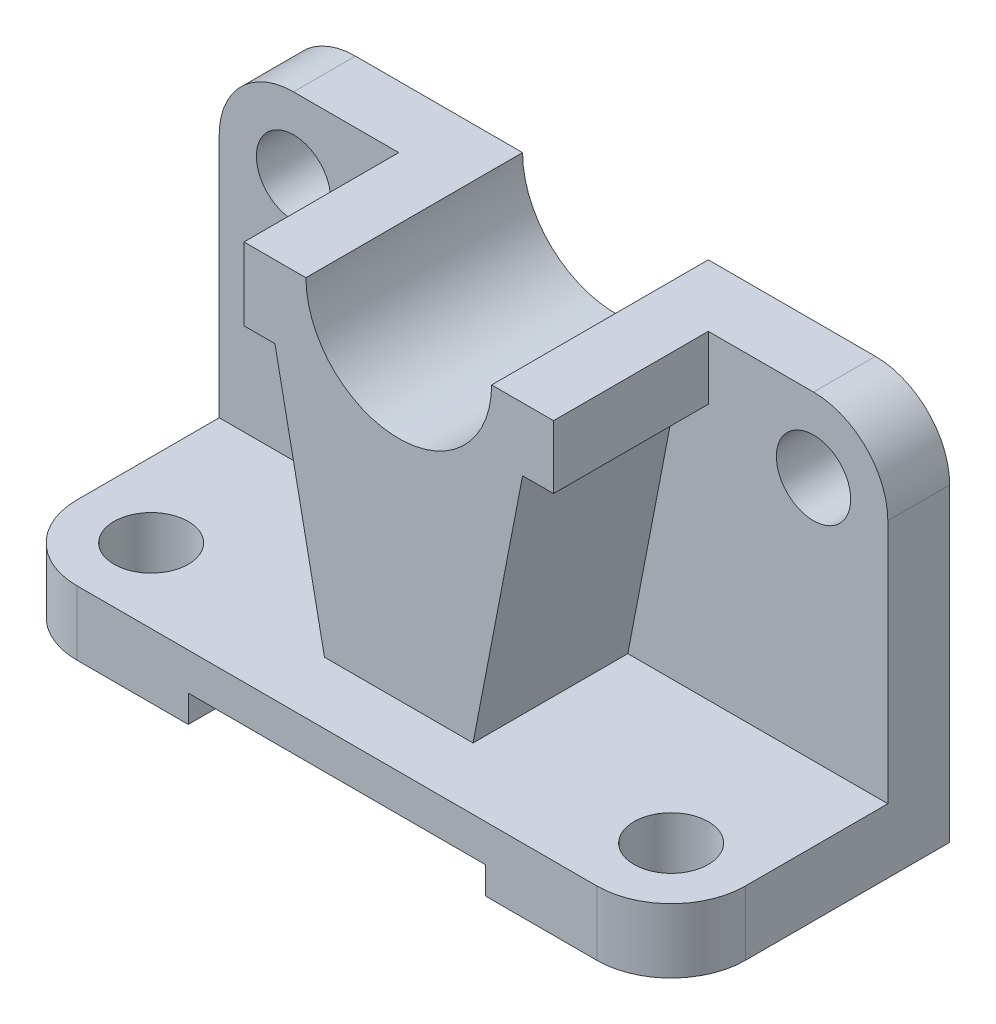
SolidWorks part; units mm, degrees
ref_plane "Front Plane" through (0, 0, 0) normal (0, 0, 1) x (1, 0, 0)
ref_plane "Top Plane" through (0, 0, 0) normal (0, 1, 0) x (1, 0, 0)
ref_plane "Right Plane" through (0, 0, 0) normal (1, 0, 0) x (0, 0, -1)
sketch "Sketch1" plane through (0, 0, 0) normal (0, 0, 1) x (1, 0, 0)
  line L0 (0, 10.4082) -> (108, 10.4082)
  line L1 (0, 0) -> (30, 0)
  line L2 (0, 0) -> (0, 62)
  line L3 (0, 62) -> (108, 62)
  line L4 (108, 0) -> (108, 62)
  line L6 (30, 0) -> (30, 4.3878)
  line L7 (30, 4.3878) -> (78, 4.3878)
  line L8 (78, 0) -> (78, 4.3878)
  line L9 (54, 0) -> (54, 62) construction
  line L10 (39, 62) -> (29, 62)
  line L11 (29, 62) -> (29, 50.2653)
  line L12 (29, 50.2653) -> (34, 50.2653)
  line L13 (69, 62) -> (79, 62)
  line L14 (79, 62) -> (79, 51.7959)
  line L15 (79, 51.7959) -> (74, 51.7959)
  line L16 (74, 51.7959) -> (66, 10.4082)
  line L17 (34, 50.2653) -> (42, 10.4082)
  line L18 (78, 0) -> (108, 0)
  arc A0 (69, 62) -> (39, 62) centre (54, 62) cw
  circle A1 centre (96, 50) radius 6
  circle A2 centre (12, 50) radius 6
  point P13 (54, 10.4082)
  dimension "D12" = 12
  dimension "D1" = 10
  dimension "D2" = 10
  dimension "D3" = 24
  dimension "D4" = 108
  dimension "D5" = 12
  dimension "D6" = 5
  dimension "D7" = 5
  dimension "D8" = 30
  dimension "D9" = 30
  dimension "D10" = 30
  dimension "D11" = 62
extrude "Boss-Extrude1" add sketch "Sketch1" along normal blind 45 contours L7 L9 L0 L2 L1 L6 | L9 L7 L8 L18 L4 L0 region at (23.5416, 5.8981, 0) region at (84.4584, 5.8981, 0)
extrude "Boss-Extrude2" add sketch "Sketch1<3>" along normal blind 10 contours L17 L12 L11 L3 L2 L0 A2 | L15 L16 L0 L4 L3 L14 A1 region at (18.6363, 33.4919, 0) region at (89.2447, 33.5823, 0)
sketch "Sketch1<3>" plane through (0, 0, 0) normal (0, 0, 1) x (1, 0, 0) same geometry as "Sketch1"
extrude "Boss-Extrude3" add sketch "Sketch1<4>" along normal blind 35 contours L0 L9 A0 L3 L11 L12 L17 | L9 L0 L16 L15 L14 L3 A0 region at (43.7264, 35.8465, 0) region at (64.0889, 35.676, 0)
sketch "Sketch1<4>" plane through (0, 0, 0) normal (0, 0, 1) x (1, 0, 0) same geometry as "Sketch1"
fillet "Fillet1" radius 12 1 edges at (0, 62, 5)
fillet "Fillet2" radius 12 1 edges at (108, 62, 5)
fillet "Fillet3" radius 12 2 edges at (108, 5.2041, 45) (0, 5.2041, 45)
sketch "Sketch2" plane through (0, 10.4082, 0) normal (0, 1, 0) x (1, 0, 0)
  line L0 (0, -33) -> (12, -33) construction
  line L1 (0, -33) -> (0, -10) construction
  line L2 (12, -33) -> (12, -45) construction
  line L3 (108, -33) -> (96, -33) construction
  line L4 (96, -33) -> (96, -45) construction
  circle A0 centre (12, -33) radius 6
  circle A1 centre (96, -33) radius 6
  dimension "D3" = 12
  dimension "D4" = 12
  dimension "D1" = 12
  dimension "D2" = 12
extrude "Cut-Extrude1" cut sketch "Sketch2" against normal through all both and the other way through all contours A0 | A1
